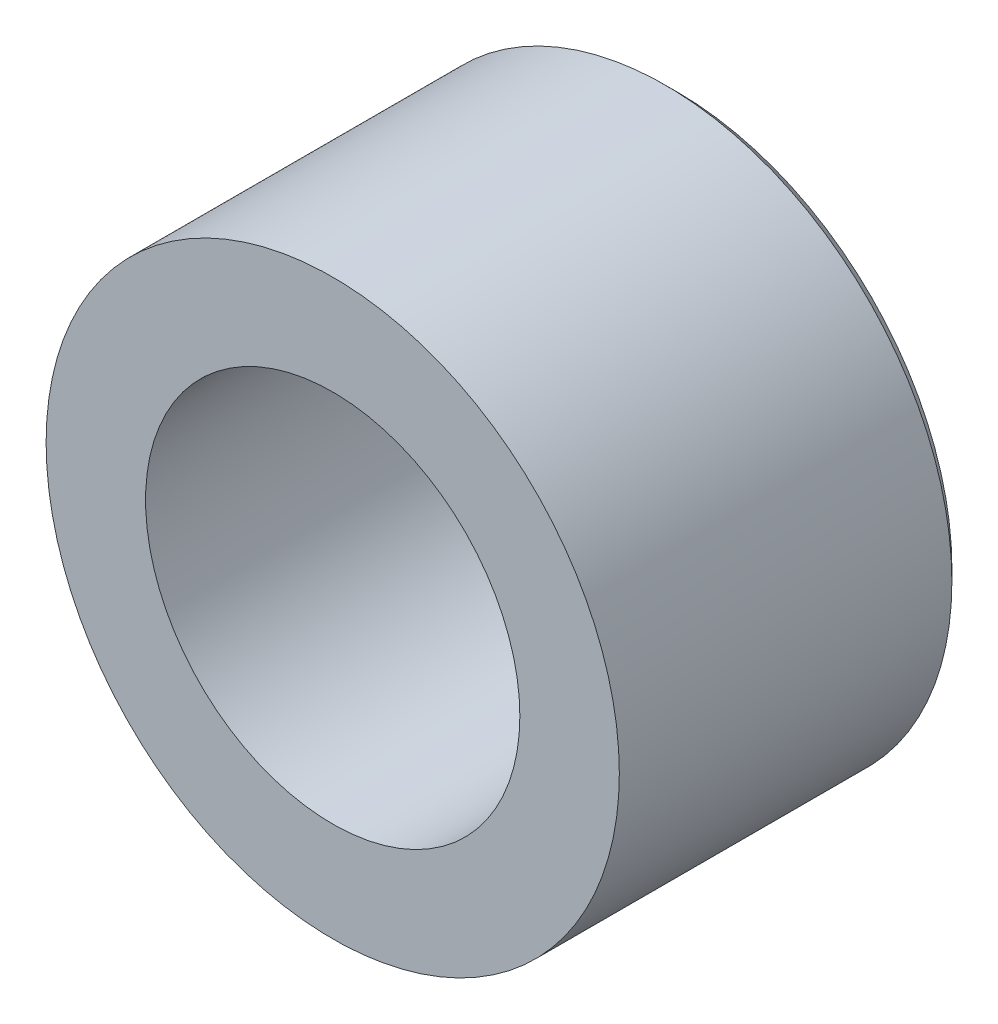
SolidWorks part; units mm, degrees
ref_plane "Front Plane" through (0, 0, 0) normal (0, 0, 1) x (1, 0, 0)
ref_plane "Top Plane" through (0, 0, 0) normal (0, 1, 0) x (1, 0, 0)
ref_plane "Right Plane" through (0, 0, 0) normal (1, 0, 0) x (0, 0, -1)
sketch "Sketch1" plane through (0, 0, 0) normal (0, 0, 1) x (1, 0, 0)
  circle A0 centre (0, 0) radius 3.175
  circle A1 centre (0, 0) radius 4.8625
  dimension "D1" = 6.35
  dimension "D2" = 9.725
extrude "Boss-Extrude1" add sketch "Sketch1" along normal blind 5.842
sketch "Sketch2" plane through (0, 0, 5.842) normal (0, 0, 1) x (1, 0, 0)
  circle A0 centre (0, 0) radius 3.175
  circle A1 centre (0, 0) radius 6.35
  dimension "D1" = 12.7
extrude "Boss-Extrude2" [suppressed] add sketch "Sketch2" along normal blind 3.175
chamfer "Chamfer1" distance 0.4 angle 45 1 edges at (3.175, 0, 0)
chamfer "Chamfer2" distance 0.2 angle 45 1 edges at (4.8625, 0, 0)
